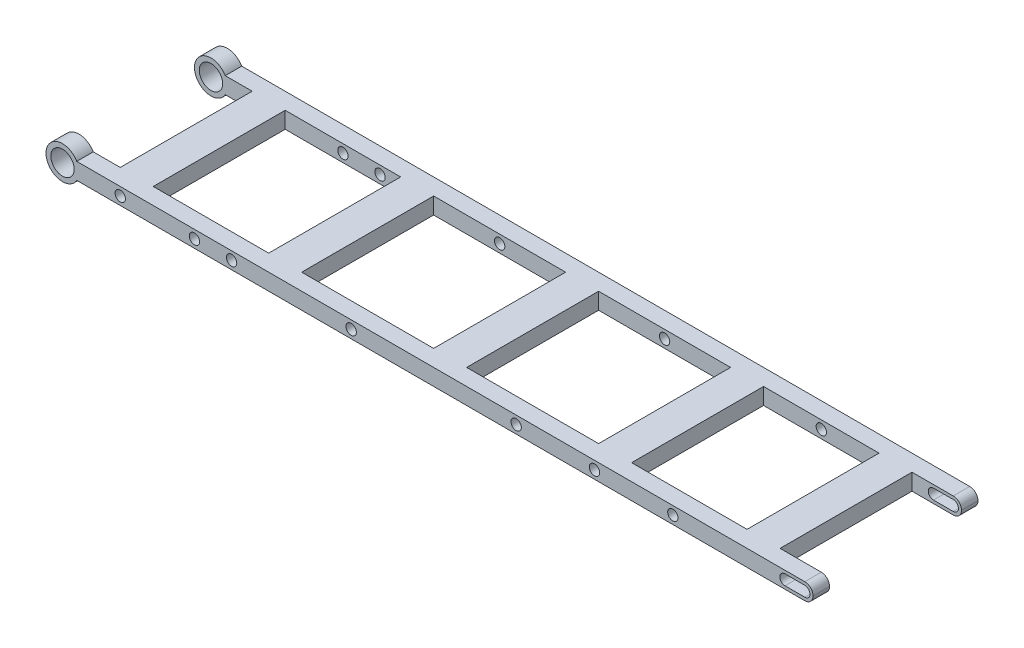
SolidWorks part; units mm, degrees
ref_plane "Front Plane" through (0, 0, 0) normal (0, 0, 1) x (1, 0, 0)
ref_plane "Top Plane" through (0, 0, 0) normal (0, 1, 0) x (1, 0, 0)
ref_plane "Right Plane" through (0, 0, 0) normal (1, 0, 0) x (0, 0, -1)
sketch "Sketch1" plane through (0, 0, 0) normal (0, 1, 0) x (1, 0, 0)
  line L0 (-146.05, 25.4) -> (-127, 25.4)
  line L1 (-146.05, 31.75) -> (146.05, 31.75)
  line L2 (-146.05, 31.75) -> (-146.05, 25.4)
  line L3 (-146.05, -31.75) -> (146.05, -31.75)
  line L4 (146.05, 31.75) -> (146.05, 25.4)
  line L5 (-146.05, 31.75) -> (146.05, -31.75) construction
  line L6 (-146.05, -31.75) -> (146.05, 31.75) construction
  line L8 (-146.05, -25.4) -> (-127, -25.4)
  line L10 (0, 31.75) -> (0, -31.75) construction
  line L11 (-6.35, 25.4) -> (-6.35, -25.4)
  line L12 (127, 25.4) -> (127, -25.4)
  line L14 (-6.35, 31.75) -> (-6.35, -31.75) construction
  line L15 (-57.15, 25.4) -> (-57.15, -25.4)
  line L20 (-69.85, 25.4) -> (-69.85, -25.4)
  line L21 (-114.3, 25.4) -> (-114.3, -25.4)
  line L22 (-127, 25.4) -> (-127, -25.4)
  line L23 (-146.05, -25.4) -> (-146.05, -31.75)
  line L24 (146.05, -25.4) -> (146.05, -31.75)
  line L32 (-114.3, 25.4) -> (-69.85, 25.4)
  line L33 (-114.3, -25.4) -> (-69.85, -25.4)
  line L36 (-57.15, -25.4) -> (-6.35, -25.4)
  line L38 (-57.15, 25.4) -> (-6.35, 25.4)
  line L47 (127, -25.4) -> (146.05, -25.4)
  line L48 (127, 25.4) -> (146.05, 25.4)
  line L50 (57.15, 25.4) -> (6.35, 25.4)
  line L51 (6.35, 25.4) -> (6.35, -25.4)
  line L52 (57.15, -25.4) -> (6.35, -25.4)
  line L53 (57.15, 25.4) -> (57.15, -25.4)
  line L54 (114.3, 25.4) -> (69.85, 25.4)
  line L55 (69.85, 25.4) -> (69.85, -25.4)
  line L56 (114.3, -25.4) -> (69.85, -25.4)
  line L57 (114.3, 25.4) -> (114.3, -25.4)
  point P0 (0, 0)
  dimension "D1" = 63.5
  dimension "D2" = 292.1
  dimension "D4" = 6.35
  dimension "D3" = 6.35
  dimension "D14" = 6.35
  dimension "D5" = 19.05
  dimension "D7" = 44.45
  dimension "D8" = 19.05
  dimension "D6" = 50.8
  dimension "D13" = 12.7
extrude "Boss-Extrude1" add sketch "Sketch1" against normal blind 6.35
fillet "Fillet2" radius 3.175 8 edges at (-146.05, -6.35, 28.575) (-146.05, 0, 28.575) (-146.05, -6.35, -28.575) (-146.05, 0, -28.575) (146.05, -6.35, -28.575) (146.05, 0, -28.575) (146.05, -6.35, 28.575) (146.05, 0, 28.575)
sketch "Sketch2" plane through (0, 0, 31.75) normal (0, 0, 1) x (1, 0, 0)
  line L0 (-142.875, 0) -> (-142.875, -6.35) construction
  line L1 (0, 0) -> (0, -6.35) construction
  line L2 (-114.3, 0) -> (-69.85, 0) construction
  line L3 (-114.3, 0) -> (-69.85, 0)
  line L4 (142.875, 0) -> (-142.875, 0)
  line L5 (-57.15, 0) -> (-6.35, 0) construction
  line L6 (-142.875, -6.35) -> (142.875, -6.35)
  line L7 (-57.15, 0) -> (-6.35, 0)
  line L8 (142.875, 0) -> (-142.875, 0)
  line L10 (-142.875, -6.35) -> (142.875, -6.35)
  line L16 (-31.75, 0) -> (-31.75, -6.35) construction
  line L17 (-92.075, 0) -> (-92.075, -6.35) construction
  line L19 (135.255, -1.1811) -> (142.875, -1.1811)
  line L20 (31.75, 0) -> (31.75, -6.35) construction
  line L21 (135.255, -5.1689) -> (142.875, -5.1689)
  line L22 (92.075, 0) -> (92.075, -6.35) construction
  line L23 (-127, 0) -> (-142.875, 0) construction
  line L24 (-127, 0) -> (-142.875, 0)
  line L25 (-127, 0) -> (-114.3, 0)
  line L26 (31.75, -3.175) -> (92.075, -3.175)
  circle A0 centre (-142.875, -3.175) radius 6.35
  circle A5 centre (-142.875, -3.175) radius 4.4996
  circle A6 centre (-92.075, -3.175) radius 1.9939
  circle A15 centre (-31.75, -3.175) radius 1.9939
  circle A16 centre (31.75, -3.175) radius 1.9939
  circle A17 centre (92.075, -3.175) radius 1.9939
  arc A19 (-142.875, 0) -> (-146.05, -3.175) centre (-142.875, -3.175) ccw
  arc A20 (-142.875, 0) -> (-146.05, -3.175) centre (-142.875, -3.175) ccw
  arc A21 (-146.05, -3.175) -> (-142.875, -6.35) centre (-142.875, -3.175) ccw
  arc A22 (-146.05, -3.175) -> (-142.875, -6.35) centre (-142.875, -3.175) ccw
  arc A23 (142.875, -6.35) -> (146.05, -3.175) centre (142.875, -3.175) ccw
  arc A24 (142.875, -6.35) -> (146.05, -3.175) centre (142.875, -3.175) ccw
  arc A25 (146.05, -3.175) -> (142.875, 0) centre (142.875, -3.175) ccw
  arc A26 (146.05, -3.175) -> (142.875, 0) centre (142.875, -3.175) ccw
  arc A27 (142.875, -5.1689) -> (142.875, -1.1811) centre (142.875, -3.175) ccw
  arc A28 (135.255, -1.1811) -> (135.255, -5.1689) centre (135.255, -3.175) ccw
  circle A29 centre (-120.65, -3.175) radius 1.9939
  circle A30 centre (61.9125, -3.175) radius 1.9939
  point P15 (-92.075, 0)
  point P46 (61.9125, -3.175)
  dimension "D1" = 12.7
  dimension "D4" = 3.9878
  dimension "D5" = 3.9878
  dimension "D6" = 31.75
  dimension "D7" = 92.075
  dimension "D11" = 8.9992
  dimension "D12" = 3.9878
  dimension "D13" = 3.9878
  dimension "D14" = 22.225
  dimension "D15" = 3.9878
  dimension "D3" = 3.9878
  dimension "D8" = 3.9878
  dimension "D10" = 7.62
  dimension "D9" = 3.9878
  dimension "D2" = 0
extrude "Boss-Extrude3" add sketch "Sketch2" along direction (0, 0, -1) on the side against the normal up to surface (6.35 mm away) contours A0 up to face at (-137.423, -3.175, 25.4)
sketch "Sketch4" plane through (0, 0, -31.75) normal (0, 0, -1) x (-1, 0, 0)
  circle A0 centre (142.875, -3.175) radius 6.35 construction
  circle A1 centre (142.875, -3.175) radius 6.35
extrude "Boss-Extrude4" add sketch "Sketch4" against normal up to surface (6.35 mm away) up to face at (-137.423, -3.175, -25.4)
extrude "Cut-Extrude1" cut sketch "Sketch2<4>" against normal up to surface (63.5 mm away) contours L19 A28 L21 A27 | A5 | A6 | A15 | A16 | A17 | A29 | A30 region at (139.065, -3.175, 31.75) up to face at (29.3029, -3.175, -31.75)
sketch "Sketch2<4>" plane through (0, 0, 31.75) normal (0, 0, 1) x (1, 0, 0) same geometry as "Sketch2"
sketch "Sketch5" plane through (127, 0, 0) normal (1, 0, 0) x (0, 0, -1)
  line L6 (25.4, -3.175) -> (25.4, -6.35) construction
  line L7 (25.4, -6.35) -> (31.75, -6.35) construction
  line L8 (31.75, -6.35) -> (31.75, -3.175) construction
  line L9 (31.75, 0) -> (25.4, 0) construction
  line L10 (25.4, 0) -> (25.4, -3.175) construction
  line L11 (31.75, -3.175) -> (31.75, 0) construction
  line L12 (-31.75, -3.175) -> (-31.75, -6.35) construction
  line L13 (-31.75, -6.35) -> (-25.4, -6.35) construction
  line L14 (-25.4, -6.35) -> (-25.4, -3.175) construction
  line L15 (-25.4, 0) -> (-31.75, 0) construction
  line L16 (-31.75, 0) -> (-31.75, -3.175) construction
  line L17 (-25.4, -3.175) -> (-25.4, 0) construction
  line L18 (25.4, -3.175) -> (25.4, -6.35) construction
  line L19 (25.4, -6.35) -> (31.75, -6.35)
  line L20 (31.75, -6.35) -> (31.75, -3.175) construction
  line L21 (31.75, 0) -> (25.4, 0) construction
  line L22 (25.4, 0) -> (25.4, -3.175) construction
  line L23 (31.75, -3.175) -> (31.75, 0) construction
  line L24 (-31.75, -3.175) -> (-31.75, -6.35) construction
  line L25 (-31.75, -6.35) -> (-25.4, -6.35)
  line L26 (-25.4, -6.35) -> (-25.4, -3.175) construction
  line L27 (-25.4, 0) -> (-31.75, 0) construction
  line L28 (-31.75, 0) -> (-31.75, -3.175) construction
  line L29 (-25.4, -3.175) -> (-25.4, 0) construction
  line L30 (-31.75, -6.35) -> (-28.575, -9.525)
  line L31 (-28.575, -9.525) -> (-25.4, -6.35)
  line L32 (25.4, -6.35) -> (28.575, -9.525)
  line L33 (28.575, -9.525) -> (31.75, -6.35)
  dimension "D1" = 45
  dimension "D2" = 45
  dimension "D3" = 45
  dimension "D4" = 45
extrude "Boss-Extrude5" add sketch "Sketch5" against normal blind 127
sketch3d "3DSketch1"
  line L0 (-57.15, 0, 25.4) -> (-69.85, 0, 25.4) construction
  line L1 (-63.5, 0, 25.4) -> (-63.5, 0, 31.75) construction
  line L2 (-137.3757, 0, 31.75) -> (142.875, 0, 31.75) construction
  line L3 (-63.5, 0, 31.75) -> (-63.5, -6.35, 31.75) construction
  line L4 (-137.3757, -6.35, 31.75) -> (0, -6.35, 31.75) construction
  line L5 (-92.075, -3.175, 31.75) -> (-63.5, -3.175, 31.75) construction
  line L6 (-92.075, -3.175, 25.4) -> (-92.075, -3.175, 31.75) construction
  circle A0 centre (-77.7875, -3.175, 31.75) radius 2
  point P11 (-63.5, -3.175, 31.75)
  point P18 (-77.7875, -3.175, 33.75)
  point P19 (-77.7875, -3.175, 31.75)
  point P20 (-77.7875, -3.175, 31.75)
  point P21 (-77.7875, -3.175, 31.75)
  point P22 (-77.7875, -3.175, 31.75)
  point P23 (-77.7875, -3.175, 31.75)
  point P24 (-77.7875, -3.175, 31.75)
  dimension "D1" = 4
extrude "Cut-Extrude2" cut sketch "3DSketch1" along direction (0, 0, 1) on the side of the normal through all
